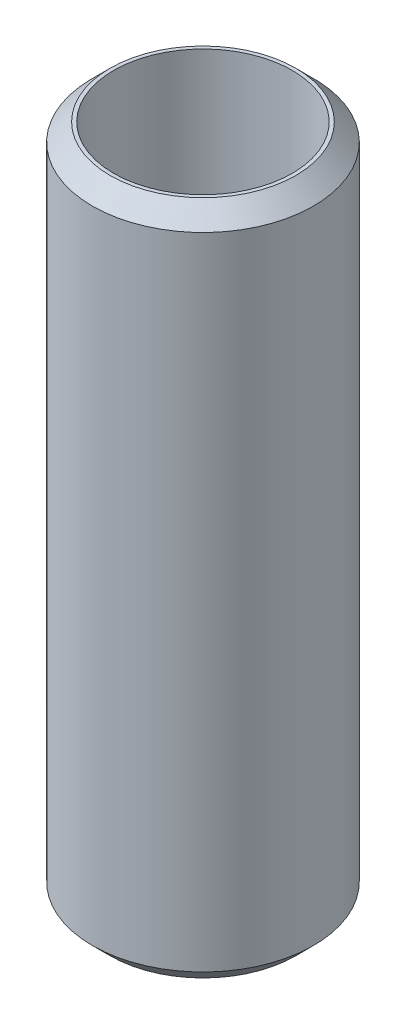
SolidWorks part; units mm, degrees
ref_plane "Front Plane" through (0, 0, 0) normal (0, 0, 1) x (1, 0, 0)
ref_plane "Top Plane" through (0, 0, 0) normal (0, 1, 0) x (1, 0, 0)
ref_plane "Right Plane" through (0, 0, 0) normal (1, 0, 0) x (0, 0, -1)
sketch "Sketch1" plane through (0, 0, 0) normal (0, 1, 0) x (1, 0, 0)
  circle A0 centre (0, 0) radius 32.5
  dimension "SHAFT_OD" = 65
extrude "Boss-Extrude1" add sketch "Sketch1" along normal blind 198.6311
sketch "Sketch2" plane through (0, 0, 0) normal (0, 1, 0) x (1, 0, 0)
  circle A0 centre (0, 0) radius 26.2408
  dimension "BORE_D" = 52.4816
extrude "Cut-Extrude1" cut sketch "Sketch2" along normal through all
chamfer "Chamfer1" distance 5.1927 angle 45 2 edges at (0, 198.6311, 32.5) (0, 0, 32.5)
